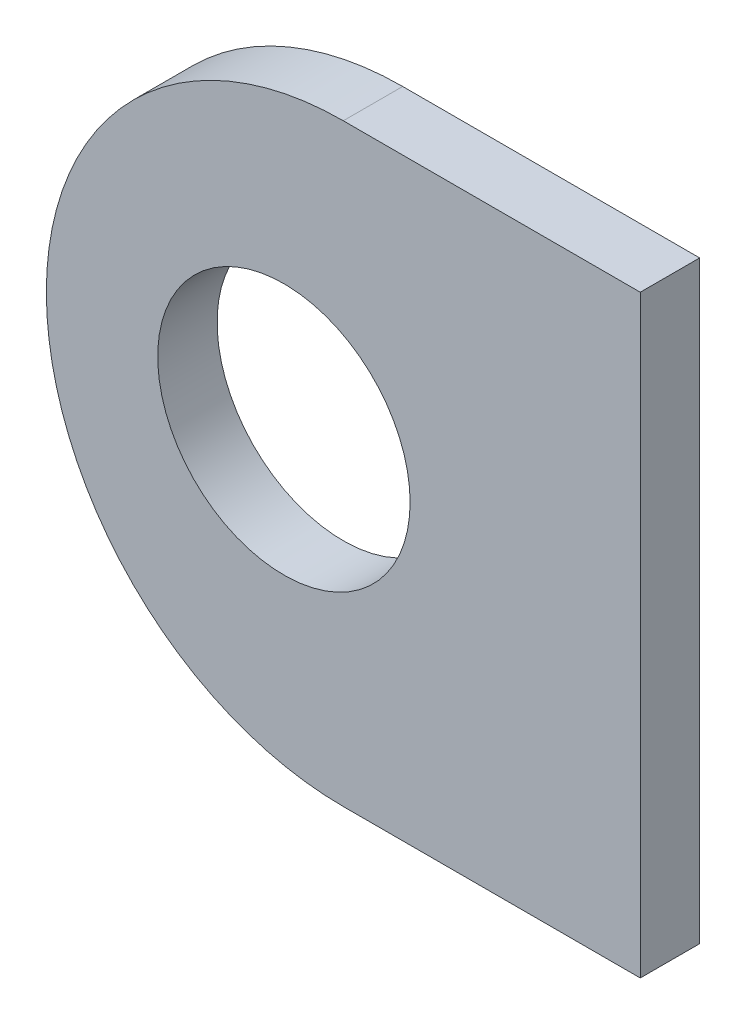
SolidWorks part; units mm, degrees
material "1.0037 (S235JR)"
ref_plane "Front Plane" through (0, 0, 0) normal (0, 0, 1) x (1, 0, 0)
ref_plane "Top Plane" through (0, 0, 0) normal (0, 1, 0) x (1, 0, 0)
ref_plane "Right Plane" through (0, 0, 0) normal (1, 0, 0) x (0, 0, -1)
sketch "Sketch2" plane through (0, 0, 0) normal (0, 0, 1) x (1, 0, 0)
  line L1 (-10, 10) -> (10, 10)
  line L2 (-10, 10) -> (-10, -10)
  line L3 (-10, -10) -> (10, -10)
  line L4 (10, 10) -> (10, -10)
  line L5 (-10, 10) -> (10, -10) construction
  line L6 (-10, -10) -> (10, 10) construction
  point P0 (0, 0)
  dimension "D1" = 20
  dimension "D2" = 20
extrude "Boss-Extrude1" add sketch "Sketch2" along normal blind 2
sketch "Sketch3" plane through (0, 0, 2) normal (0, 0, 1) x (1, 0, 0)
  circle A0 centre (-2, 0) radius 4.25
  dimension "D1" = 8.5
  dimension "D2" = 2
extrude "Cut-Extrude1" cut sketch "Sketch3" against normal through all
fillet "Fillet1" radius 10 2 edges at (-10, -10, 1) (-10, 10, 1)
